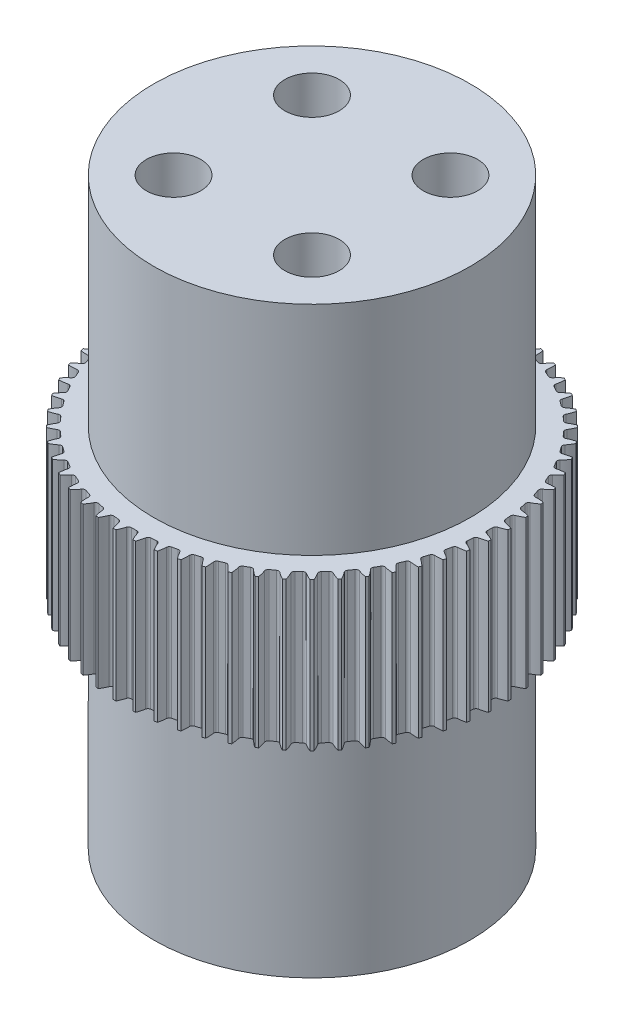
SolidWorks part; units mm, degrees
ref_plane "Front Plane" through (0, 0, 0) normal (0, 0, 1) x (1, 0, 0)
ref_plane "Top Plane" through (0, 0, 0) normal (0, 1, 0) x (1, 0, 0)
ref_plane "Right Plane" through (0, 0, 0) normal (1, 0, 0) x (0, 0, -1)
sketch "Sketch1" plane through (0, 0, 0) normal (0, 1, 0) x (1, 0, 0)
  circle A0 centre (0, 0) radius 19
extrude "Boss-Extrude1" add sketch "Sketch1" along normal blind 15
sketch "Sketch2" plane through (0, 15, 0) normal (0, 1, 0) x (1, 0, 0)
  line L0 (-0.2687, 18) -> (0.2687, 18)
  arc A1 (0.2687, 18) -> (0.5569, 18.2167) centre (0.2687, 18.3) ccw
  circle A2 centre (0, 0) radius 8
  arc A3 (0.5569, 18.2167) -> (1, 19.25) centre (4.9375, 16.95) cw
  arc A4 (-0.5569, 18.2167) -> (-1, 19.25) centre (-4.9375, 16.95) ccw
  arc A5 (-1, 19.25) -> (1, 19.25) centre (0, 16.031) cw
  arc A6 (-0.5569, 18.2167) -> (-0.2687, 18) centre (-0.2687, 18.3) ccw
  point P12 (0.5, 18)
  dimension "D1" = 3.3708
  dimension "D4" = 4.56
  dimension "D5" = 0.3
  dimension "D2" = 0.5
  dimension "D3" = 1.25
extrude "Cut-Extrude1" cut sketch "Sketch2" against normal through all
pattern_circular "CirPattern1" count 60 over 360 about axis through (0, 15, 0) along (0, -1, 0) of "Cut-Extrude1"
sketch "Sketch3" plane through (0, 15, 0) normal (0, 1, 0) x (1, 0, 0)
  circle A0 centre (0, 0) radius 8
extrude "Boss-Extrude2" add sketch "Sketch3" against normal blind 15
sketch "Sketch4" plane through (0, 15, 0) normal (0, 1, 0) x (1, 0, 0)
  circle A0 centre (0, 0) radius 16
extrude "Boss-Extrude3" add sketch "Sketch4" along normal blind 22
sketch "Sketch5" plane through (0, 0, 0) normal (0, -1, 0) x (1, 0, 0)
  circle A1 centre (0, 0) radius 16
extrude "Boss-Extrude4" add sketch "Sketch5" along normal blind 22
sketch "Sketch6" plane through (0, -22, 0) normal (0, -1, 0) x (1, 0, 0)
  line L1 (-7, -7) -> (7, -7)
  line L2 (-7, -7) -> (-7, 7)
  line L3 (-7, 7) -> (7, 7)
  line L4 (7, -7) -> (7, 7)
  line L5 (-7, -7) -> (7, 7) construction
  line L6 (-7, 7) -> (7, -7) construction
  circle A0 centre (0, 0) radius 1.5002
  circle A1 centre (-7, 7) radius 2.75
  circle A2 centre (7, 7) radius 2.75
  circle A3 centre (7, -7) radius 2.75
  circle A4 centre (-7, -7) radius 2.75
  dimension "D1" = 14
  dimension "D2" = 14
extrude "Cut-Extrude2" cut sketch "Sketch6" against normal blind 125 contours L3 A1 L2 | L2 A1 L3 | L4 A2 L3 | L1 A3 L4 | L2 A4 L1 | L1 A4 L2 | L4 A3 L1 | L3 A2 L4 region at (-5.8329, -22, -5.8329) region at (-7.389, -22, -7.389) region at (5.8329, -22, -5.8329) region at (7.389, -22, -7.389) region at (-7.389, -22, 7.389) region at (-5.8329, -22, 5.8329) region at (5.8329, -22, 5.8329) region at (7.389, -22, 7.389)
